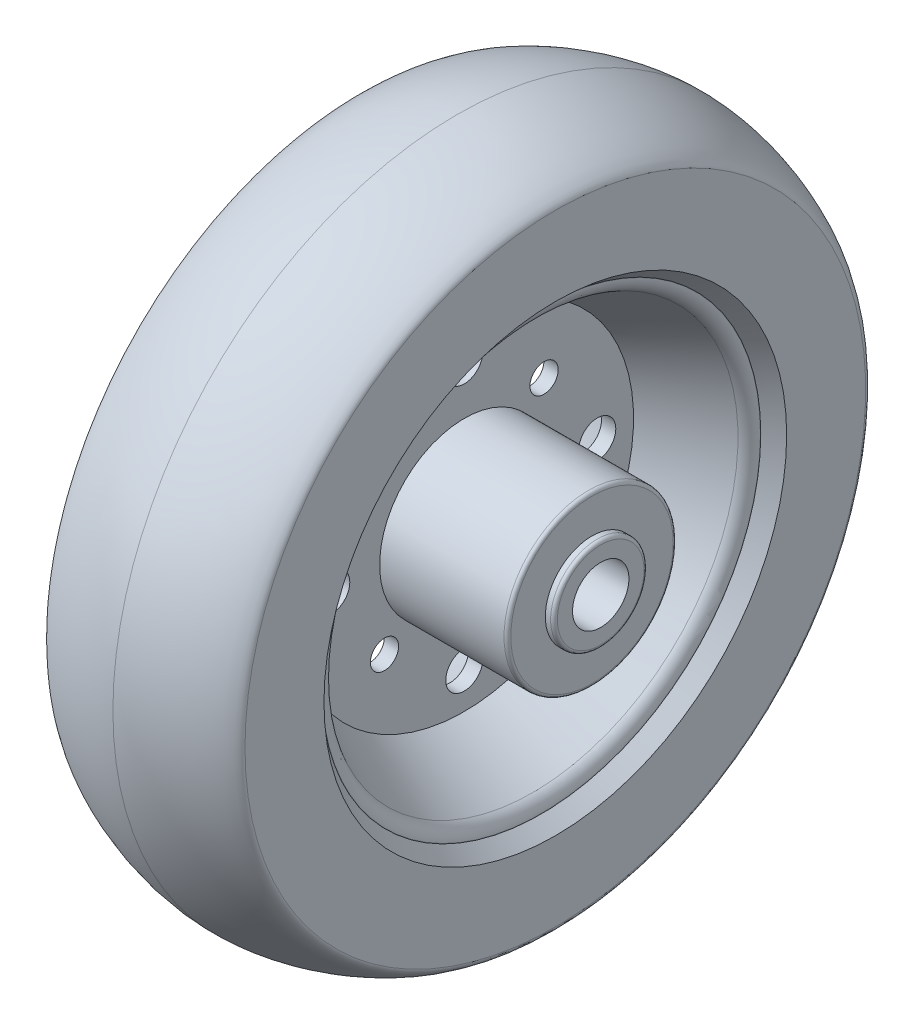
SolidWorks part; units mm, degrees
ref_plane "Front Plane" through (0, 0, 0) normal (0, 0, 1) x (1, 0, 0)
ref_plane "Top Plane" through (0, 0, 0) normal (0, 1, 0) x (1, 0, 0)
ref_plane "Right Plane" through (0, 0, 0) normal (1, 0, 0) x (0, 0, -1)
sketch "Sketch5" plane through (0, 0, 0) normal (0, 0, 1) x (1, 0, 0)
  line L0 (-22.1043, 0) -> (-22.1043, 69.85)
  line L1 (0, -1000) -> (0, 49000) construction
  line L2 (-22.1043, 0) -> (22.1043, 0) construction
  line L3 (22.1043, 0) -> (22.1043, 69.85)
  line L4 (-22.1043, 73.6345) -> (-22.1043, 66.0655) construction
  line L5 (2.3783, 77.47) -> (-2.3783, 77.47) construction
  line L6 (-22.1043, 0) -> (22.1043, 0)
  spline S0 degree 3 poles (-22.1043, 69.85) (-22.1043, 72.068) (-10.5362, 77.47) (0, 77.47) knots 0 0 0 0 1 1 1 1
  spline S1 degree 3 poles (22.1043, 69.85) (22.1043, 72.068) (10.5362, 77.47) (0, 77.47) knots 0 0 0 0 1 1 1 1
  point P8 (0, 0)
  dimension "D1" = 77.47
  dimension "D2" = 69.85
  dimension "D3" = 44.2087
revolve "Revolve1" add sketch "Sketch5" angle 360 about L6
sketch "Sketch7" plane through (0, 0, 0) normal (0, 1, 0) x (1, 0, 0)
  line L0 (-1000, 0) -> (49000, 0) construction
  line L1 (1.6129, 0) -> (1.6129, 38.1)
  line L2 (1.6129, 38.1) -> (17.0264, 46.1924)
  line L3 (18.9293, 49.3409) -> (18.9293, 49.4128)
  line L4 (18.9293, 49.4128) -> (22.1043, 52.07)
  line L5 (22.1043, -69.85) -> (22.1043, 69.85) construction
  line L6 (22.1043, 52.07) -> (22.1043, 0)
  line L7 (1.6129, 0) -> (22.1043, 0)
  line L8 (0, -77.47) -> (0, 77.47) construction
  arc A0 (17.0264, 46.1924) -> (18.9293, 49.3409) centre (15.3733, 49.3409) ccw
  point P12 (18.9293, 47.1915)
  dimension "D3" = 19.558
  dimension "D7" = 3.556
  dimension "D1" = 52.07
  dimension "D2" = 4.1402
  dimension "D4" = 38.1
  dimension "D5" = 1.6129
  dimension "D6" = 3.175
revolve "Cut-Revolve2" cut sketch "Sketch7" angle 360 about L0
mirror "Mirror1" about plane through (0, 0, 0) normal (1, 0, 0) of "Cut-Revolve2"
sketch "Sketch8" plane through (1.6129, 0, 0) normal (1, 0, 0) x (0, 0, -1)
  circle A1 centre (0, 0) radius 19.05
  dimension "D1" = 38.1
extrude "Boss-Extrude1" add sketch "Sketch8" along normal blind 28.7528
sketch "Sketch9" plane through (30.3657, 0, 0) normal (1, 0, 0) x (0, 0, -1)
  circle A0 centre (0, 0) radius 10.5156
  dimension "D1" = 21.0312
extrude "Boss-Extrude2" add sketch "Sketch9" along normal blind 1.9558
sketch "Sketch11" plane through (1.6129, 0, 0) normal (1, 0, 0) x (0, 0, -1)
  line L0 (0, 29.9339) -> (0, 0) construction
  line L1 (0, 0) -> (17.9605, 17.9605) construction
  circle A0 centre (0, 29.9339) radius 4.1656
  circle A1 centre (17.9605, 17.9605) radius 3.175
  circle A2 centre (29.9339, 0) radius 4.1656
  circle A3 centre (0, -29.9339) radius 4.1656
  circle A4 centre (-29.9339, 0) radius 4.1656
  circle A5 centre (17.9605, -17.9605) radius 3.175
  circle A6 centre (-17.9605, -17.9605) radius 3.175
  circle A7 centre (-17.9605, 17.9605) radius 3.175 [skipped]
  circle A8 centre (17.9605, 17.9605) radius 6.35 construction
  dimension "D2" = 8.3312
  dimension "D4" = 6.35
  dimension "D7" = 45
  dimension "D1" = 25.7683
  dimension "D5" = 25.4
  dimension "D3" = 4
  dimension "D6" = 4
extrude "Cut-Extrude6" cut sketch "Sketch11" against normal through all
sketch "Sketch12" plane through (-1.6129, 0, 0) normal (-1, 0, 0) x (0, 0, 1)
  circle A0 centre (0, 0) radius 19.05
  dimension "D1" = 38.1
extrude "Boss-Extrude3" add sketch "Sketch12" along normal blind 27.6606
sketch "Sketch13" plane through (-29.2735, 0, 0) normal (-1, 0, 0) x (0, 0, 1)
  circle A0 centre (0, 0) radius 10.306
  dimension "D1" = 20.6121
extrude "Boss-Extrude4" add sketch "Sketch13" along normal blind 2.2352
fillet "Fillet4" radius 0.762 4 edges at (32.3215, 0, -10.5156) (30.3657, 0, -19.05) (-31.5087, 0, 10.306) (-29.2735, 0, 19.05)
sketch "Sketch14" plane through (32.3215, 0, 0) normal (1, 0, 0) x (0, 0, -1)
  circle A0 centre (0, 0) radius 6.35
  dimension "D1" = 12.7
extrude "Cut-Extrude7" cut sketch "Sketch14" against normal through all
